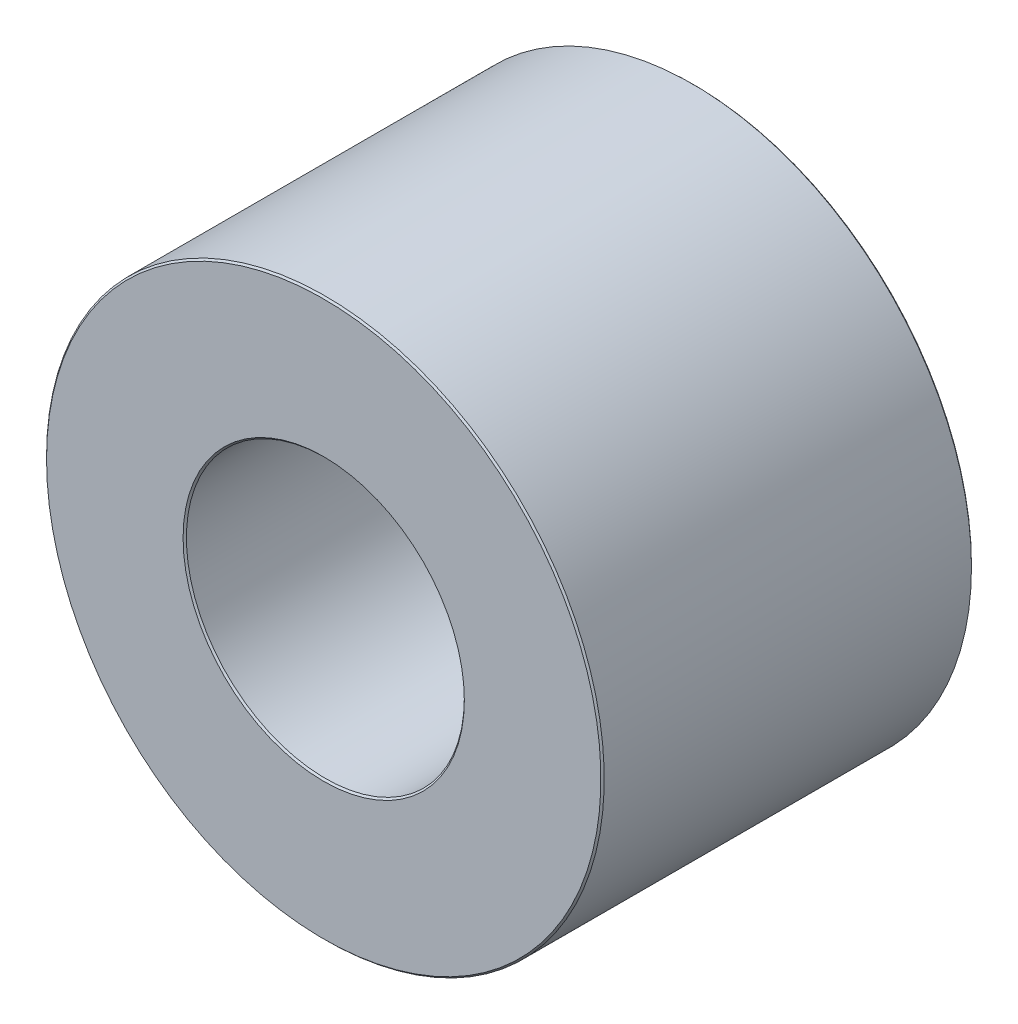
SolidWorks part; units mm, degrees
ref_plane "Front Plane" through (0, 0, 0) normal (0, 0, 1) x (1, 0, 0)
ref_plane "Top Plane" through (0, 0, 0) normal (0, 1, 0) x (1, 0, 0)
ref_plane "Right Plane" through (0, 0, 0) normal (1, 0, 0) x (0, 0, -1)
sketch "Sketch1" plane through (0, 0, 0) normal (0, 0, 1) x (1, 0, 0)
  circle A0 centre (0, 0) radius 3.01
  circle A1 centre (0, 0) radius 1.5
  point P8 (0, -3.01)
  point P9 (0, 3.01)
  dimension "ID" = 3
  dimension "OD" = 6.02
sketch "Sketch2" plane through (0, 0, 0) normal (1, 0, 0) x (0, 0, -1)
  line L0 (2, 0) -> (-2, 0) construction
  line L1 (2, 3.01) -> (-2, 3.01) construction
  point P4 (0, 0)
  point P8 (0, 3.01)
  point P9 (0, 3.01)
  dimension "Length" = 4
sketch "Sketch5" plane through (0, 0, 0) normal (0, 0, 1) x (1, 0, 0)
  circle A0 centre (0, 0) radius 1.5 construction
  circle A1 centre (0, 0) radius 3.01 construction
  circle A2 centre (0, 0) radius 1.5
  circle A3 centre (0, 0) radius 3.01
extrude "Boss-Extrude1" add sketch "Sketch5" along normal up to vertex and the other way up to vertex up to point (0, 0, 2) other way up to point (0, 0, -2)
chamfer "Chamfer1" distance 0.018 angle 45 4 edges at (3.01, 0, -2) (1.5, 0, -2) (1.5, 0, 2) (3.01, 0, 2)
equation "\"D1@Chamfer1\"=\"ID@Sketch1\"*.006"
